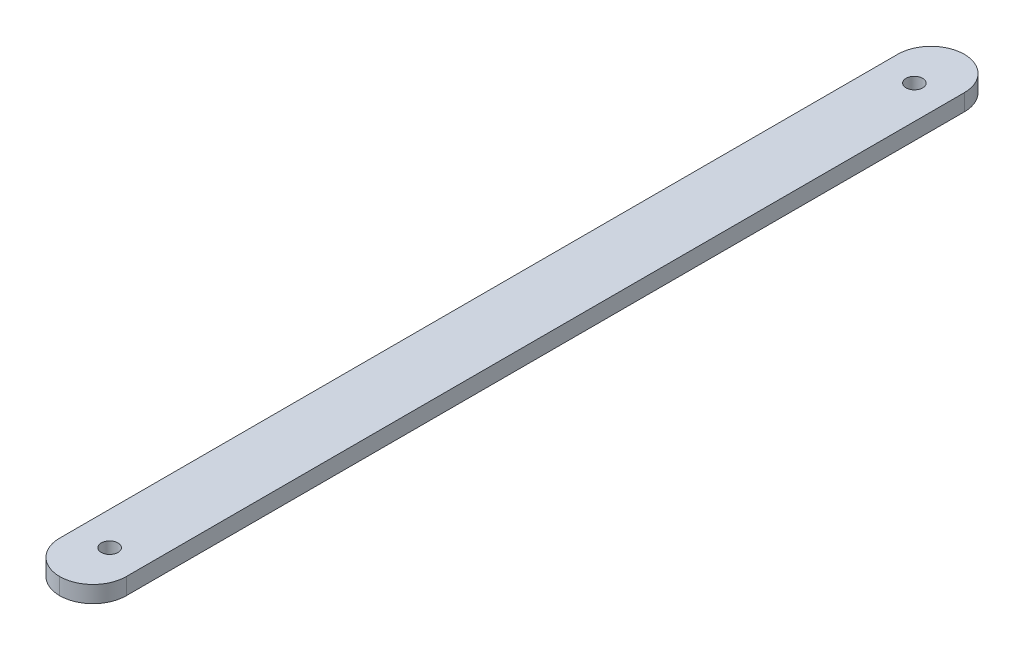
SolidWorks part; units mm, degrees
ref_plane "前视基准面" through (0, 0, 0) normal (0, 0, 1) x (1, 0, 0)
ref_plane "上视基准面" through (0, 0, 0) normal (0, 1, 0) x (1, 0, 0)
ref_plane "右视基准面" through (0, 0, 0) normal (1, 0, 0) x (0, 0, -1)
other "Configuration Table"
sketch "草图1" plane through (0, 0, 0) normal (0, 0, 1) x (1, 0, 0)
  line L1 (17.7065, 4.903) -> (-2.2935, 4.903)
  line L2 (17.7065, 4.903) -> (17.7065, -0.097)
  line L3 (17.7065, -0.097) -> (-2.2935, -0.097)
  line L4 (-2.2935, 4.903) -> (-2.2935, -0.097)
  line L5 (17.7065, 4.903) -> (-2.2935, -0.097) construction
  line L6 (17.7065, -0.097) -> (-2.2935, 4.903) construction
  point P0 (7.7065, 2.403)
  dimension "D1" = 20
  dimension "D2" = 5
extrude "凸台-拉伸1" add sketch "草图1" along normal blind 271.75
sketch "草图2" plane through (0, 0, 0) normal (0, 1, 0) x (1, 0, 0)
  line L0 (17.7065, 0) -> (-2.2935, 0) construction
  line L2 (17.7065, -271.75) -> (-2.2935, -271.75) construction
  line L3 (17.7065, -271.75) -> (17.7065, 0) construction
  line L4 (-2.2935, -271.75) -> (-2.2935, 0) construction
  circle A0 centre (7.7065, -15) radius 2.5
  circle A1 centre (7.7065, -256.75) radius 2.5
  dimension "D1" = 5
  dimension "D2" = 15
  dimension "D3" = 5
  dimension "D4" = 10
  dimension "D5" = 15
  dimension "D6" = 10
extrude "切除-拉伸1" cut sketch "草图2" against normal mid plane 251.75
fillet "圆角1" radius 10 4 edges at (-2.2935, 2.403, 0) (17.7065, 2.403, 0) (-2.2935, 2.403, 271.75) (17.7065, 2.403, 271.75)
